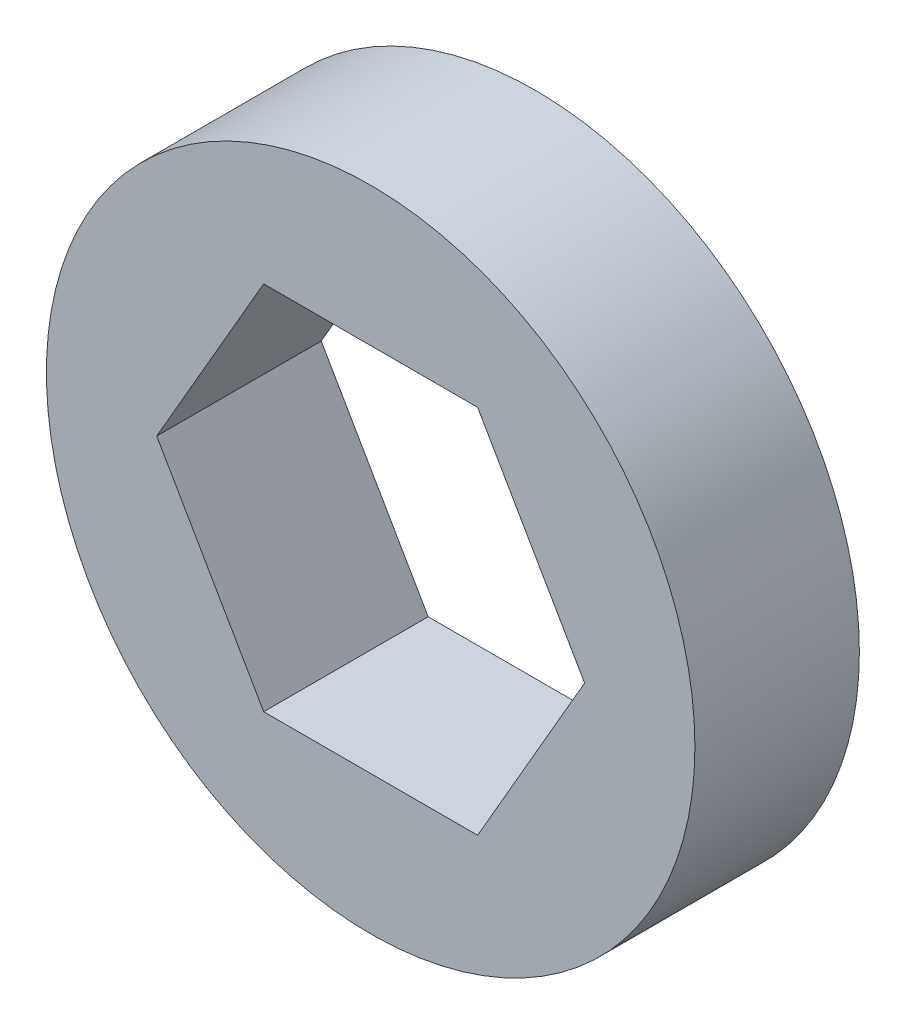
SolidWorks part; units mm, degrees
material "Nylon 101"
ref_plane "Front Plane" through (0, 0, 0) normal (0, 0, 1) x (1, 0, 0)
ref_plane "Top Plane" through (0, 0, 0) normal (0, 1, 0) x (1, 0, 0)
ref_plane "Right Plane" through (0, 0, 0) normal (1, 0, 0) x (0, 0, -1)
sketch "Sketch1" plane through (0, 0, 0) normal (0, 0, 1) x (1, 0, 0)
  line L1 (3.6662, 6.35) -> (-3.6662, 6.35)
  line L2 (-3.6662, 6.35) -> (-7.3323, 0)
  line L3 (-7.3323, 0) -> (-3.6662, -6.35)
  line L4 (-3.6662, -6.35) -> (3.6662, -6.35)
  line L5 (3.6662, -6.35) -> (7.3323, 0)
  line L6 (7.3323, 0) -> (3.6662, 6.35)
  circle A1 centre (0, 0) radius 11.1125
  circle A2 centre (0, 0) radius 6.35 construction
  dimension "D1" = 22.225
  dimension ".5" = 12.7
extrude "Boss-Extrude1" add sketch "Sketch1" along normal blind 5.6375
sketch "Sketch2" plane through (0, 0, 0) normal (0, 0, -1) x (-1, 0, 0)
  line L0 (-3.6079, 6.985) -> (3.4241, 6.985) construction
  line L1 (-3.6662, 6.35) -> (3.6662, 6.35) construction
  text T0 "0048" font "Century Gothic" height in points 6
  point P5 (0, 0)
  point P6 (-2.2937, 9.9984)
  dimension "D1" = 0.635
extrude "Cut-Extrude1" cut sketch "Sketch2" against normal blind 0.4
